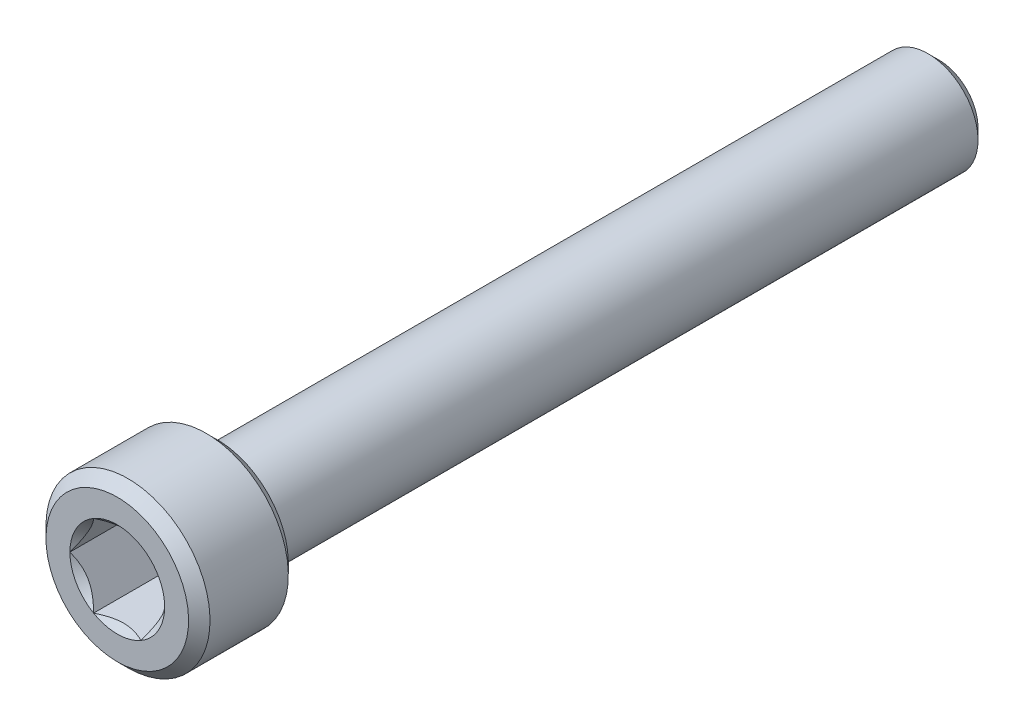
SolidWorks part; units mm, degrees
ref_plane "Front Plane" through (0, 0, 0) normal (0, 0, 1) x (1, 0, 0)
ref_plane "Top Plane" through (0, 0, 0) normal (0, 1, 0) x (1, 0, 0)
ref_plane "Right Plane" through (0, 0, 0) normal (1, 0, 0) x (0, 0, -1)
sketch "Sketch1" plane through (0, 0, 0) normal (1, 0, 0) x (0, 0, -1)
  line L0 (-10.3124, 0) -> (24.6126, 0) construction
  line L1 (-10.3124, 3.9688) -> (-10.3124, -3.9688) construction
  line L2 (24.6126, 2.413) -> (24.6126, -2.413) construction
  line L3 (24.6126, 2.413) -> (25.4063, 2.413) construction
  line L4 (-10.3124, 3.9688) -> (-15.1384, 3.9688) construction
  line L5 (-15.1384, -1.9844) -> (-15.1384, 1.9844) construction
  point P5 (0, 2.413)
  point P6 (22.6282, -2.413)
  point P9 (24.6126, 0)
  point P14 (-15.1384, 0)
  dimension "Pitch" = 0.7937
  dimension "Thread OD" = 4.826
  dimension "Thread Length" = 24.6126
  dimension "Head Dia" = 7.9375
  dimension "Head Height" = 4.826
  dimension "Length" = 34.925
  dimension "Drive Size" = 3.9688
  dimension "D1" = 1.9844
sketch "Sketch2" plane through (0, 0, 0) normal (1, 0, 0) x (0, 0, -1)
  line L0 (-15.1384, 0) -> (24.6126, 0)
  line L1 (-14.6198, 3.9688) -> (-10.831, 3.9688)
  line L2 (-15.1384, 3.4502) -> (-15.1384, 0)
  line L4 (-10.3124, 3.4502) -> (-10.3124, 2.413)
  line L5 (24.6126, 0) -> (24.6126, 1.8944)
  line L6 (24.094, 2.413) -> (-10.3124, 2.413)
  line L7 (-10.3124, 3.4502) -> (-10.831, 3.9688)
  line L8 (-15.1384, 3.4502) -> (-14.6198, 3.9688)
  line L9 (24.094, 2.413) -> (24.6126, 1.8944)
  line L10 (-10.3124, 3.9688) -> (-15.1384, 3.9688) construction
  line L11 (-10.3124, 3.9688) -> (-10.3124, -3.9688) construction
  point P0 (-12.7254, 3.9688)
  dimension "D1" = 45
  dimension "D2" = 0.5186
revolve "Revolve1" add sketch "Sketch2" angle 360 about L0
sketch "Sketch3" plane through (0, 0, 15.1384) normal (0, 0, 1) x (1, 0, 0)
  line L1 (1.1457, 1.9844) -> (-1.1457, 1.9844)
  line L2 (-1.1457, 1.9844) -> (-2.2914, 0)
  line L3 (-2.2914, 0) -> (-1.1457, -1.9844)
  line L4 (-1.1457, -1.9844) -> (1.1457, -1.9844)
  line L5 (1.1457, -1.9844) -> (2.2914, 0)
  line L6 (2.2914, 0) -> (1.1457, 1.9844)
  circle A0 centre (0, 0) radius 1.9844 construction
extrude "Cut-Extrude1" cut sketch "Sketch3" against normal blind 3.6195
sketch "Sketch4" plane through (0, 0, 15.1384) normal (0, 0, 1) x (1, 0, 0)
  circle A0 centre (0, 0) radius 2.2914
extrude "Cut-Extrude2" cut sketch "Sketch4" against normal through all draft 45
split "Split1" [suppressed] bodies to split 106
sketch "Sketch6" [suppressed] plane through (0, 0, -24.6126) normal (0, 0, -1) x (-1, 0, 0)
  line L0 (0, -1.9844) -> (0, 1.9844) construction
  circle A0 centre (0, 0) radius 2.413
sketch "Sketch7" [suppressed] plane through (0, 0, 0) normal (1, 0, 0) x (0, 0, -1)
  line L0 (24.6126, 2.413) -> (25.3071, 2.413) construction
  line L1 (25.3071, 2.413) -> (24.9599, 1.8115) construction
  line L2 (24.9599, 1.8115) -> (24.6126, 2.413) construction
  line L3 (24.6126, 2.413) -> (24.563, 2.4989) construction
  line L4 (24.563, 2.4989) -> (25.3567, 2.4989) construction
  line L5 (25.3567, 2.4989) -> (25.3071, 2.413) construction
  line L6 (24.9103, 1.8974) -> (25.0095, 1.8974) construction
  line L7 (24.9599, 2.413) -> (24.9599, 2.4989) construction
  line L8 (24.9599, 1.8974) -> (24.9599, 1.8115) construction
  line L9 (24.6126, 2.413) -> (25.4063, 2.413) construction
  dimension "D1" = 0.0992
curve "Helix/Spiral1" [suppressed] pitch 0.7937 height 26.2001 turns 33.008
sketch "Sketch8" [suppressed] plane through (0, 0, 0) normal (1, 0, 0) x (0, 0, -1)
  line L0 (24.5878, 2.456) -> (25.3319, 2.456)
  line L1 (24.6126, 2.413) -> (24.563, 2.4989) construction
  line L2 (25.3567, 2.4989) -> (25.3071, 2.413) construction
  line L3 (25.3319, 2.456) -> (25.0095, 1.8974)
  line L4 (25.0095, 1.8974) -> (24.9103, 1.8974)
  line L5 (24.9103, 1.8974) -> (24.5878, 2.456)
sweep "Cut-Sweep1" [suppressed] cut profiles "Sketch8" path "Helix/Spiral1"
combine bodies "Combine1" [suppressed] operation type add bodies to combine 109 107
equation "\"D1@Cut-Extrude1\"=\"Head Height@Sketch1\"*.75"
equation "\"D2@Sketch2\"=(\"Head Dia@Sketch1\"-\"Thread OD@Sketch1\")/6"
equation "\"D3@Helix/Spiral1\"=\"Thread Length@Sketch1\"+(2*\"Pitch@Sketch1\")"
equation "\"D1@Sketch7\"=\"Pitch@Sketch1\"/8"
equation "\"D4@Helix/Spiral1\"=\"Pitch@Sketch1\""
equation "\"D1@Sketch1\"=\"Pitch@Sketch1\"*2.5"
